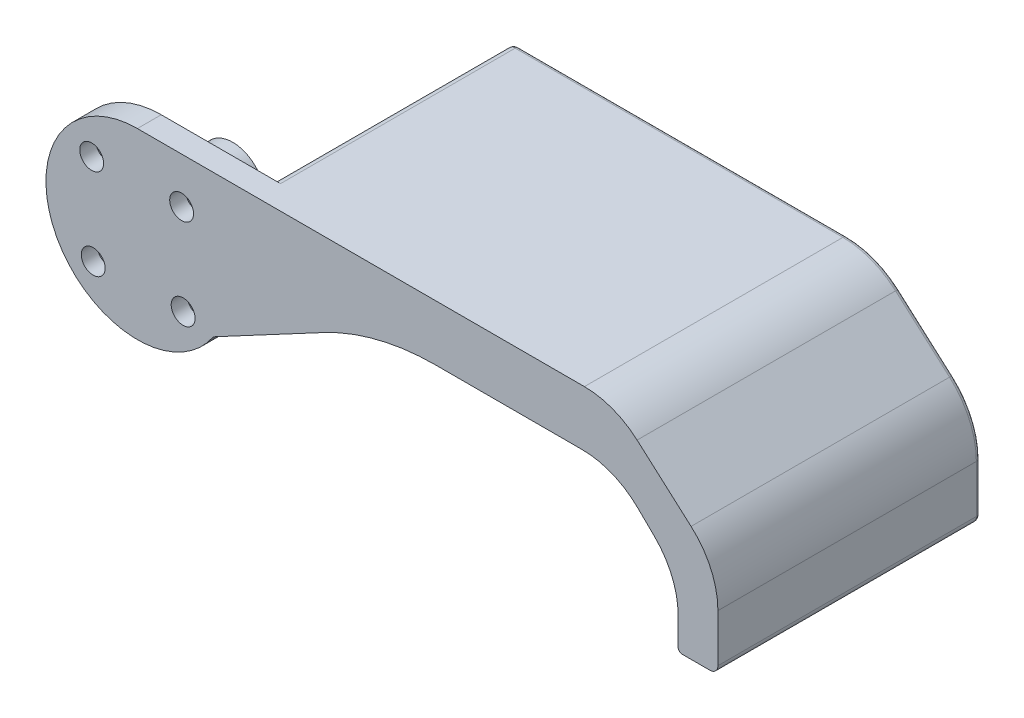
SolidWorks part; units mm, degrees
ref_plane "Płaszczyzna przednia" through (0, 0, 0) normal (0, 0, 1) x (1, 0, 0)
ref_plane "Płaszczyzna górna" through (0, 0, 0) normal (0, 1, 0) x (1, 0, 0)
ref_plane "Płaszczyzna prawa" through (0, 0, 0) normal (1, 0, 0) x (0, 0, -1)
sketch "Szkic1" plane through (0, 0, 0) normal (0, 0, 1) x (1, 0, 0)
  circle A0 centre (68.25, -14) radius 11.5
extrude "Dodanie-wyciągnięcie1" add sketch "Szkic1" along normal blind 3 contours A0
sketch "Szkic2" plane through (0, 0, 0) normal (0, 0, -1) x (-1, 0, 0)
  circle A0 centre (-68.25, -14) radius 4
extrude "Dodanie-wyciągnięcie2" add sketch "Szkic2" along normal blind 9
sketch "Szkic3" plane through (0, 0, 3) normal (0, 0, 1) x (1, 0, 0)
  circle A0 centre (74.0009, -19.5612) radius 1.5
  circle A1 centre (73.8112, -8.2491) radius 1.5
  circle A2 centre (62.4991, -8.4388) radius 1.5
  circle A3 centre (62.6888, -19.7509) radius 1.5
extrude "Wytnij-wyciągnięcie1" cut sketch "Szkic3" against normal blind 2
sketch "Szkic4" plane through (0, 0, 3) normal (0, 0, 1) x (1, 0, 0)
  line L0 (68.25, -2.5) -> (128.25, -2.5)
  line L1 (128.25, -25.5) -> (141.25, -25.5) construction
  line L3 (128.25, -2.5) -> (128.25, -25.5) construction
  line L5 (68.25, -25.5) -> (128.25, -25.5) construction
  line L6 (79.75, -14) -> (128.25, -14) construction
  line L7 (98.25, -2.5) -> (98.25, -9.5) construction
  line L8 (128.25, -2.5) -> (128.25, -9.5) construction
  line L10 (98.25, -9.5) -> (68.25, -25.5) construction
  line L11 (141.25, -25.5) -> (136.25, -25.5)
  line L13 (128.25, -14) -> (141.25, -14) construction
  line L14 (141.25, -25.5) -> (141.25, -14)
  line L17 (98.25, -9.5) -> (77.8002, -20.4066)
  line L18 (77.8002, -20.4066) -> (76.8953, -6.4166)
  line L19 (76.8953, -6.4166) -> (68.25, -2.5)
  line L20 (141.25, -14) -> (128.25, -2.5)
  line L21 (141.25, -14) -> (136.25, -14) construction
  line L22 (136.25, -14) -> (136.25, -9.5769) construction
  line L23 (136.25, -17.3166) -> (128.25, -9.5)
  line L24 (136.25, -25.5) -> (136.25, -17.3166)
  line L25 (136.25, -17.3166) -> (141.25, -14) construction
  line L26 (128.25, -9.5) -> (98.25, -9.5)
  circle A0 centre (68.25, -14) radius 11.5 construction
extrude "Dodanie-wyciągnięcie3" add sketch "Szkic4" against normal blind 3
sketch "Szkic6" plane through (0, 0, 0) normal (0, 0, -1) x (-1, 0, 0)
  line L1 (-128.25, -2.5) -> (-68.25, -2.5) construction
  line L3 (-82.25, -2.5) -> (-128.25, -2.5)
  line L4 (-128.25, -2.5) -> (-141.25, -14)
  line L5 (-141.25, -14) -> (-141.25, -25.5)
  line L6 (-141.25, -25.5) -> (-136.25, -25.5)
  line L7 (-136.25, -25.5) -> (-136.25, -24.5)
  line L8 (-136.25, -17.3166) -> (-136.25, -25.5) construction
  line L9 (-141.25, -24.5) -> (-139.75, -24.5) construction
  line L10 (-136.25, -24.5) -> (-139.75, -24.5)
  line L11 (-141.25, -14) -> (-138.8355, -14.4686) construction
  line L12 (-138.8355, -14.4686) -> (-140.128, -13.0075) construction
  line L13 (-139.75, -24.5) -> (-139.75, -14.901)
  line L14 (-128.25, -2.5) -> (-127.9174, -4.876) construction
  line L15 (-127.9174, -4.876) -> (-129.2425, -3.378) construction
  line L16 (-138.8355, -14.4686) -> (-127.9174, -4.876) construction
  line L17 (-120.4787, -2.5) -> (-120.4787, -4.5) construction
  line L18 (-120.4787, -4.5) -> (-127.97, -4.5) construction
  line L19 (-127.9174, -4.876) -> (-127.4894, -4.5) construction
  line L20 (-139.75, -14.901) -> (-127.4894, -4.5)
  line L21 (-127.4894, -4.5) -> (-82.25, -4.5)
  line L22 (-82.25, -4.5) -> (-82.25, -2.5)
  line L24 (-139.75, -24.5) -> (-139.75, -25.5) construction
extrude "Dodanie-wyciągnięcie4" add sketch "Szkic6" along normal blind 30
fillet "Zaokrąglenie1" radius 10 6 edges at (128.25, -2.5, -13.5) (141.25, -14, -13.5) (136.25, -17.3166, 1.5) (128.25, -9.5, 1.5) (139.75, -14.901, -15) (127.4894, -4.5, -15)
fillet "Zaokrąglenie2" radius 30 1 edges at (98.25, -9.5, 1.5)
fillet "Zaokrąglenie6" radius 1 4 edges at (141.25, -25.5, -13.5) (139.75, -24.5, -15) (82.25, -2.5, -15) (82.25, -4.5, -15)
fillet "Zaokrąglenie8" radius 0.5 2 edges at (136.25, -25.5, -13.5) (136.25, -24.5, -15)
fillet "Zaokrąglenie9" radius 0.5 18 edges at (139.4571, -24.2071, -30) (137.75, -24.5, -30) (136.3964, -24.6464, -30) (136.3964, -25.3536, -30) (138.5, -25.5, -30) (82.5429, -2.7929, -30) (82.5429, -4.2071, -30) (140.9571, -25.2071, -30) (139.75, -21.5157, -30) (141.25, -21.5025, -30) (138.8244, -15.3296, -30) (140.3675, -14.3976, -30) (133.2537, -9.39, -30) (127.2647, -5.1123, -30) (134.4816, -8.0126, -30) (128.0043, -3.1485, -30) (103.8558, -2.5, -30) (103.5346, -4.5, -30)
move or copy body "Obiekt-Przenieś/Kopiuj1" [suppressed] bodies to move or copy 105 parameters "D1"=0, "D2"=0, "D3"=0
